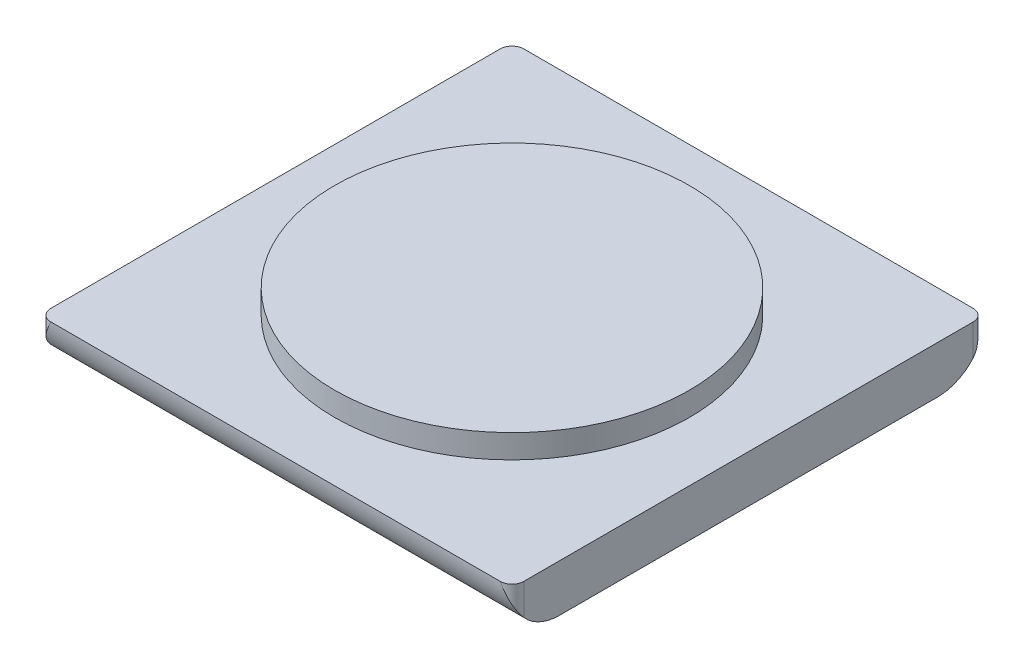
SolidWorks part; units mm, degrees
ref_plane "Front Plane" through (0, 0, 0) normal (0, 0, 1) x (1, 0, 0)
ref_plane "Top Plane" through (0, 0, 0) normal (0, 1, 0) x (1, 0, 0)
ref_plane "Right Plane" through (0, 0, 0) normal (1, 0, 0) x (0, 0, -1)
sketch "Turntable Sketch" plane through (0, 0, 0) normal (0, 1, 0) x (1, 0, 0)
  circle A0 centre (0, 0) radius 75
  dimension "D1" = 150
extrude "Turntable Extrude" add sketch "Turntable Sketch" along normal blind 10
sketch "Support Plate Sketch" plane through (0, 0, 0) normal (0, 1, 0) x (1, 0, 0)
  line L1 (-100, 100) -> (100, 100)
  line L2 (-100, 100) -> (-100, -100)
  line L3 (-100, -100) -> (100, -100)
  line L4 (100, 100) -> (100, -100)
  line L5 (-100, 100) -> (100, -100) construction
  line L6 (-100, -100) -> (100, 100) construction
  point P0 (0, 0)
  dimension "D1" = 200
  dimension "D2" = 200
extrude "Support Plate Extrude" add sketch "Support Plate Sketch" against normal blind 20 separate body
fillet "Support Plate Fillet" radius 5 4 edges at (-100, -10, 100) (-100, -10, -100) (100, -10, -100) (100, -10, 100)
fillet "Bottom Fillet" radius 20 2 edges at (0, -20, -100) (0, -20, 100) tangent propagation no
